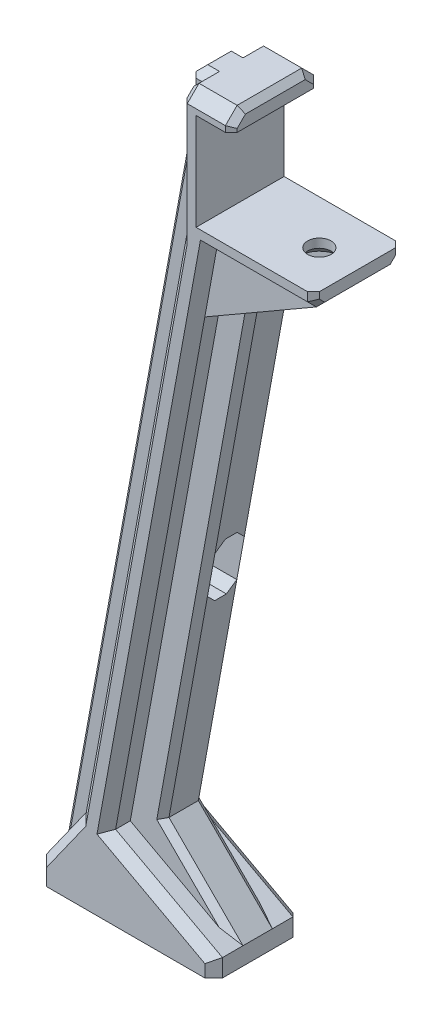
SolidWorks part; units mm, degrees
ref_plane "Plano frontal" through (0, 0, 0) normal (0, 0, 1) x (1, 0, 0)
ref_plane "Plano superior" through (0, 0, 0) normal (0, 1, 0) x (1, 0, 0)
ref_plane "Plano direito" through (0, 0, 0) normal (1, 0, 0) x (0, 0, -1)
sketch "Esboço1" plane through (0, 0, 0) normal (0, 0, 1) x (1, 0, 0)
  line L1 (47.5, 7.5) -> (-47.5, 7.5) construction
  line L2 (47.5, 7.5) -> (47.5, -7.5) construction
  line L3 (47.5, -7.5) -> (-47.5, -7.5) construction
  line L4 (-47.5, 7.5) -> (-47.5, -7.5) construction
  point P0 (0, 0)
  dimension "D1" = 15
  dimension "D2" = 95
sketch "Esboço2" plane through (0, 0, 0) normal (0, 0, 1) x (1, 0, 0)
  line L5 (47.5, -7.5) -> (-47.5, -7.5) construction
  line L6 (-41.65, 8.85) -> (-41.65, 11.85)
  line L7 (-41.65, 11.85) -> (-50.65, 11.85)
  line L8 (-50.65, 11.85) -> (-50.65, -10.65)
  line L14 (-47.65, -7.65) -> (-27.65, -7.65)
  line L15 (-47.65, 8.85) -> (-47.65, -7.65)
  line L17 (-50.65, -10.65) -> (-27.65, -10.65)
  line L19 (-41.65, 8.85) -> (-47.65, 8.85)
  line L41 (-27.65, -7.65) -> (-27.65, -10.65)
  dimension "D2" = 6
  dimension "D3" = 3
  dimension "D4" = 0.15
  dimension "D5" = 3
  dimension "D6" = 20
  dimension "D12" = 3
  dimension "D7" = 16.5
extrude "Ressalto-extrusão1" add sketch "Esboço2" along normal blind 15
ref_plane "Plano1" through (0, -117.65, 0) normal (0, -1, 0) x (-1, 0, 0)
sketch "Esboço7" plane through (0, -117.65, 0) normal (0, -1, 0) x (-1, 0, 0)
  line L0 (50.65, -15) -> (50.65, 0) construction
  line L1 (44.65, 0) -> (74.65, 0)
  line L2 (44.65, 0) -> (44.65, -15)
  line L3 (44.65, -15) -> (74.65, -15)
  line L4 (74.65, 0) -> (74.65, -15)
  point P0 (50.65, -7.5)
  dimension "D1" = 15
  dimension "D2" = 30
  dimension "D4" = 24
extrude "Ressalto-extrusão3" add sketch "Esboço7" against normal blind 3 separate body
sketch "Esboço8" plane through (0, -10.65, 0) normal (0, -1, 0) x (1, 0, 0)
  line L0 (47.5, 0) -> (-47.5, 0) construction
  line L1 (-50.65, 15) -> (-45.65, 15)
  line L2 (-50.65, 15) -> (-50.65, 0)
  line L3 (-50.65, 0) -> (-45.65, 0)
  line L4 (-45.65, 15) -> (-45.65, 0)
  dimension "D1" = 5
sketch "Esboço9" plane through (0, -114.65, 0) normal (0, 1, 0) x (1, 0, 0)
  line L0 (-74.65, -15) -> (-74.65, 0) construction
  line L1 (-74.65, 0) -> (-44.65, 0) construction
  line L2 (-69.65, -15) -> (-64.65, -15)
  line L3 (-69.65, -15) -> (-69.65, 0)
  line L4 (-69.65, 0) -> (-64.65, 0)
  line L5 (-64.65, -15) -> (-64.65, 0)
  line L6 (-69.65, -15) -> (-64.65, 0) construction
  line L7 (-69.65, 0) -> (-64.65, -15) construction
  point P4 (-67.15, -7.5)
  dimension "D1" = 5
  dimension "D2" = 5
loft "Loft3" add profiles "Esboço9", "Esboço8"
sketch "Esboço14" plane through (-42.2927, 7.7266, 0) normal (0.9837, -0.1797, 0) x (0, 0, -1)
  line L2 (-11, -16.6486) -> (-11, -124.402)
  line L3 (-11, -124.402) -> (-4, -124.402)
  line L4 (-4, -16.6486) -> (-4, -124.402)
  line L5 (-15, -124.402) -> (0, -124.402) construction
  line L6 (0, -124.402) -> (0, -18.6807) construction
  line L7 (-15, -124.402) -> (-15, -18.6807) construction
  line L8 (-11, -16.6486) -> (-4, -16.6486)
  dimension "D1" = 4
  dimension "D2" = 4
extrude "Ressalto-extrusão5" add sketch "Esboço14" along normal blind 2
sketch "Esboço15" plane through (-47.1313, 8.6105, 0) normal (-0.9837, 0.1797, 0) x (0, 0, 1)
  line L0 (15, -19.5793) -> (0, -19.5793) construction
  line L1 (4, -19.5793) -> (11, -19.5793)
  line L2 (4, -19.5793) -> (4, -127.4322)
  line L3 (4, -127.4322) -> (11, -127.4322)
  line L4 (11, -19.5793) -> (11, -127.4322)
  line L5 (0, -125.3006) -> (0, -19.5793) construction
  line L6 (15, -125.3006) -> (15, -19.5793) construction
  dimension "D1" = 4
  dimension "D2" = 4
extrude "Ressalto-extrusão6" add sketch "Esboço15" along normal blind 2
sketch "Esboço16" plane through (-50.65, 0, 0) normal (-1, 0, 0) x (0, 0, 1)
  line L0 (15, 11.85) -> (0, 11.85) construction
  line L2 (4, -10.65) -> (4, 11.85)
  line L3 (4, 11.85) -> (11, 11.85)
  line L4 (11, -10.65) -> (11, 11.85)
  line L6 (11, -10.65) -> (4, -10.65) construction
  line L7 (11, -10.65) -> (4, -10.65)
extrude "Ressalto-extrusão9" add sketch "Esboço16" along normal blind 2
chamfer "Chanfro11" distance 10 angle 72 1 edges
chamfer "Chanfro12" distance 10 angle 25 1 edges
chamfer "Chanfro13" distance 2 angle 45 2 edges at (-46.15, 11.85, 0) (-46.15, 11.85, 15)
chamfer "Chanfro14" distance 4.8 angle 45 1 edges at (-43.6169, -10.65, 7.5)
chamfer "Chanfro16" distance 1.5 angle 45 22 edges at (-50.65, 11.85, 3) (-51.65, 11.85, 11) (-51.65, 11.85, 4) (-52.65, 11.85, 7.5) (-53.7514, -109.7244, 0) (-53.7514, -109.7244, 15) (-71.2514, -109.6034, 15) (-71.2514, -109.6034, 0) (-50.65, 11.85, 12) (-50.65, -0.4, 0) (-50.65, 10.85, 1) (-50.65, -0.4, 15) (-50.65, 10.85, 14) (-74.65, -116.0219, 0) (-74.65, -116.0219, 15) (-44.65, -116.1429, 15) (-44.65, -116.1429, 0)
chamfer "Chanfro17" distance 1.5 angle 45 2 edges
chamfer "Chanfro18" distance 1 angle 45 8 edges at (-52.65, -0.0594, 4) (-61.6205, -59.5707, 4) (-52.65, -0.0594, 11) (-61.6205, -59.5707, 11) (-41.0631, -13.0109, 4) (-52.7409, -60.5917, 4) (-41.0631, -13.0109, 11) (-52.7409, -60.5917, 11)
sketch "Esboço17" plane through (0, -10.65, 0) normal (0, -1, 0) x (1, 0, 0)
  line L0 (-37.6468, 7.5) -> (-27.65, 7.5) construction
  line L1 (-37.6468, 10) -> (-37.6468, 5) construction
  line L2 (-27.65, 13.5) -> (-27.65, 1.5) construction
  circle A0 centre (-34.15, 7.5) radius 2
  dimension "D1" = 4
  dimension "D2" = 6.5
extrude "Corte-extrusão1" cut sketch "Esboço17" against normal blind 5
chamfer "Chanfro20" distance 1 angle 45 10 edges at (-27.65, -8.4, 0) (-27.65, -9.9, 0.75) (-27.65, -10.65, 7.5) (-27.65, -9.9, 14.25) (-27.65, -8.4, 15) (-41.65, 9.35, 0) (-41.65, 10.85, 1) (-41.65, 11.85, 7.5) (-41.65, 10.85, 14) (-41.65, 9.35, 15)
sketch "Esboço18" plane through (0, 0, 11) normal (0, 0, 1) x (1, 0, 0)
  line L0 (-44.65, -114.6359) -> (-57.2608, -102.0251)
  line L1 (-45.65, -10.65) -> (-62.8528, -104.8128) construction
  line L3 (-64.6474, -114.6359) -> (-44.65, -114.6359)
  line L5 (-51.65, -10.5594) -> (-69.2219, -106.7427) construction
  line L6 (-74.65, -114.3939) -> (-64.6474, -114.6359)
  line L7 (-67.5749, -97.7275) -> (-61.5584, -97.7275)
  line L9 (-52.65, 10.35) -> (-51.65, 10.35)
  line L10 (-51.65, 10.35) -> (-51.65, -10.5594)
  line L11 (-51.65, -10.5594) -> (-67.5749, -97.7275)
  line L12 (-60.6989, -98.587) -> (-61.5584, -97.7275)
  line L13 (-40.2932, -9.15) -> (-57.2608, -102.0251)
  line L14 (-61.9275, -105.3122) -> (-45.3888, -14.7847) construction
  line L15 (-60.6989, -98.587) -> (-44.3594, -9.15)
  line L16 (-46.9008, -9.15) -> (-28.65, -9.15) construction
  line L17 (-44.3594, -9.15) -> (-40.2932, -9.15)
  line L18 (-74.65, -114.3939) -> (-52.65, 6.0272)
  line L21 (-52.65, 6.0272) -> (-52.65, 10.35)
  dimension "D1" = 45
  dimension "D2" = 4
extrude "Ressalto-extrusão10" add sketch "Esboço18" against normal blind 7
ref_plane "Plano2" through (0, 0, 1.5) normal (0, 0, -1) x (-1, 0, 0)
sketch "Esboço19" plane through (0, 0, 1.5) normal (0, 0, -1) x (-1, 0, 0)
  line L2 (28.65, -10.65) -> (49.3592, -22.6064)
  line L3 (46.9008, -9.15) -> (64.5243, -105.6153) construction
  line L4 (49.3592, -22.6064) -> (46.9008, -9.15)
  line L5 (46.9008, -9.15) -> (46.9008, -7.65)
  line L6 (28.65, -7.65) -> (47.65, -7.65) construction
  line L7 (46.9008, -7.65) -> (28.65, -7.65)
  line L8 (45.65, -10.65) -> (28.65, -10.65) construction
  line L9 (28.65, -10.65) -> (28.65, -7.65)
  dimension "D1" = 30
extrude "Ressalto-extrusão11" add sketch "Esboço19" against normal blind 2
ref_plane "Plano3" through (0, 0, 13.5) normal (0, 0, 1) x (1, 0, 0)
sketch "Esboço21" plane through (0, 0, 13.5) normal (0, 0, 1) x (1, 0, 0)
  line L2 (-28.65, -10.65) -> (-49.3592, -22.6064) construction
  line L3 (-49.3592, -22.6064) -> (-46.9008, -9.15) construction
  line L4 (-46.9008, -9.15) -> (-46.9008, -7.65) construction
  line L5 (-46.9008, -7.65) -> (-28.65, -7.65) construction
  line L8 (-28.65, -10.65) -> (-49.3592, -22.6064)
  line L9 (-49.3592, -22.6064) -> (-46.9008, -9.15)
  line L10 (-46.9008, -9.15) -> (-46.9008, -7.65)
  line L11 (-46.9008, -7.65) -> (-28.65, -7.65)
  line L12 (-28.65, -10.65) -> (-28.65, -7.65)
extrude "Ressalto-extrusão13" add sketch "Esboço21" against normal blind 2
sketch "Esboço23" plane through (0, 0, 0) normal (1, 0, 0) x (0, 0, -1)
  line L1 (-10, -57.65) -> (-5, -57.65)
  line L2 (-10, -57.65) -> (-10, -67.65)
  line L3 (-10, -67.65) -> (-5, -67.65)
  line L4 (-5, -57.65) -> (-5, -67.65)
  line L6 (-1.5, -117.65) -> (-13.5, -117.65) construction
  line L7 (-7.5, -7.65) -> (-7.5, -117.65) construction
  line L9 (-10, -57.65) -> (-5, -67.65) construction
  line L10 (-5, -57.65) -> (-10, -67.65) construction
  point P4 (-7.5, -62.65)
  point P10 (-7.5, -62.65)
  dimension "D1" = 5
  dimension "D2" = 10
extrude "Corte-extrusão2" cut sketch "Esboço23" against normal blind 60
chamfer "Chanfro22" distance 1.5 angle 45 4 edges at (-55.4904, -67.65, 5) (-55.4904, -67.65, 10) (-54.5769, -57.65, 5) (-54.5769, -57.65, 10)
chamfer "Chanfro21" distance 1 angle 45 8 edges at (-50.9554, -108.3305, 11) (-50.9554, -108.3305, 4) (-48.9979, -56.7969, 11) (-48.9979, -56.7969, 4) (-52.65, 8.1886, 4) (-63.65, -54.1834, 11) (-63.65, -54.1834, 4) (-52.65, 8.1886, 11)
sketch "Esboço24" plane through (-60, 0, 0) normal (1, 0, 0) x (0, 0, -1)
  line L12 (-5.15, -59.2121) -> (-6.5621, -57.8) construction
  line L13 (-6.5621, -57.8) -> (-8.4379, -57.8) construction
  line L14 (-8.4379, -57.8) -> (-9.85, -59.2121) construction
  line L15 (-9.85, -59.2121) -> (-9.85, -66.0879) construction
  line L16 (-9.85, -66.0879) -> (-8.4379, -67.5) construction
  line L17 (-8.4379, -67.5) -> (-6.5621, -67.5) construction
  line L18 (-6.5621, -67.5) -> (-5.15, -66.0879) construction
  line L19 (-5.15, -66.0879) -> (-5.15, -59.2121) construction
sketch "Esboço25" plane through (0, -10.65, 0) normal (0, -1, 0) x (1, 0, 0)
  line L0 (-28.65, 7.5) -> (-42.4732, 7.5) construction
  line L1 (-28.65, 3.5) -> (-28.65, 11.5) construction
ref_plane "Plano4" through (0, 0, 7.5) normal (0, 0, 1) x (1, 0, 0)
sketch "Esboço26" plane through (0, 0, 7.5) normal (0, 0, 1) x (1, 0, 0)
  line L5 (-34.15, -7.15) -> (-34.15, -10.65)
  line L7 (-28.65, -10.65) -> (-42.4732, -10.65) construction
  line L10 (-34.15, -10.65) -> (-34.15, -11.7032)
  line L11 (-34.15, -11.7032) -> (-30.65, -11.7032)
  line L12 (-30.65, -11.7032) -> (-30.65, -10.65)
  line L13 (-30.65, -10.65) -> (-34.15, -7.15)
  dimension "D2" = 3.5
  dimension "D3" = 45
revolve "Corte-Revolução1" cut sketch "Esboço26" angle 360 about L5
